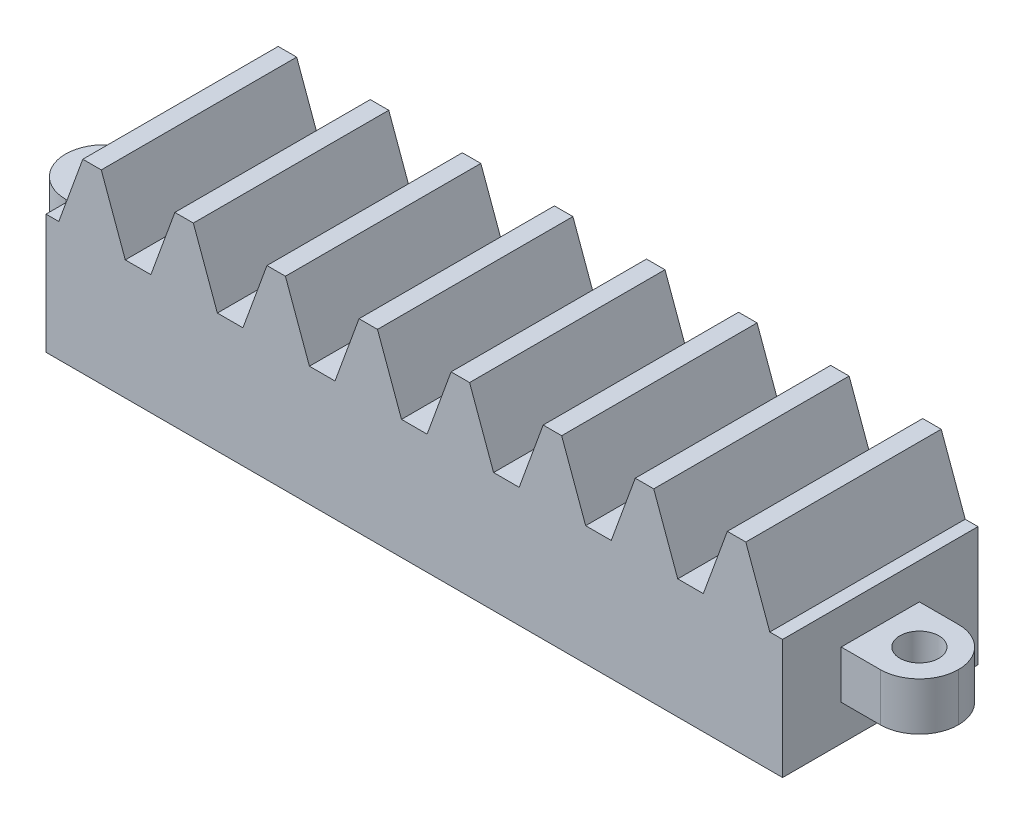
SolidWorks part; units mm, degrees
ref_plane "Plane1" through (0, 0, 0) normal (0, 0, 1) x (1, 0, 0)
ref_plane "Plane2" through (0, 0, 0) normal (0, 1, 0) x (1, 0, 0)
ref_plane "Plane3" through (0, 0, 0) normal (1, 0, 0) x (0, 0, -1)
sketch "Croquis3" plane through (0, 0, 0) normal (0, 0, 1) x (1, 0, 0)
  line B0 (32.3321, 6.125) -> (31.1037, 9.5)
  line B1 (33.6414, 6.125) -> (32.3321, 6.125)
  line B2 (34.8698, 9.5) -> (33.6414, 6.125)
  line B3 (35.8161, 9.5) -> (34.8698, 9.5)
  line B4 (37.0445, 6.125) -> (35.8161, 9.5)
  line B5 (37.6991, 6.125) -> (37.0445, 6.125)
  line B6 (0, 0) -> (37.6991, 0)
  line B7 (22.9073, 6.125) -> (21.6789, 9.5)
  line B8 (24.2166, 6.125) -> (22.9073, 6.125)
  line B9 (25.445, 9.5) -> (24.2166, 6.125)
  line B10 (26.3913, 9.5) -> (25.445, 9.5)
  line B11 (27.6197, 6.125) -> (26.3913, 9.5)
  line B12 (28.929, 6.125) -> (27.6197, 6.125)
  line B13 (30.1574, 9.5) -> (28.929, 6.125)
  line B14 (31.1037, 9.5) -> (30.1574, 9.5)
  line B15 (13.4825, 6.125) -> (12.2541, 9.5)
  line B16 (14.7918, 6.125) -> (13.4825, 6.125)
  line B17 (16.0202, 9.5) -> (14.7918, 6.125)
  line B18 (16.9665, 9.5) -> (16.0202, 9.5)
  line B19 (18.1949, 6.125) -> (16.9665, 9.5)
  line B20 (19.5042, 6.125) -> (18.1949, 6.125)
  line B21 (20.7326, 9.5) -> (19.5042, 6.125)
  line B22 (21.6789, 9.5) -> (20.7326, 9.5)
  line B23 (4.0577, 6.125) -> (2.8293, 9.5)
  line B24 (5.367, 6.125) -> (4.0577, 6.125)
  line B25 (6.5954, 9.5) -> (5.367, 6.125)
  line B26 (7.5417, 9.5) -> (6.5954, 9.5)
  line B27 (8.7701, 6.125) -> (7.5417, 9.5)
  line B28 (10.0794, 6.125) -> (8.7701, 6.125)
  line B29 (11.3078, 9.5) -> (10.0794, 6.125)
  line B30 (12.2541, 9.5) -> (11.3078, 9.5)
  line B31 (37.6991, 6.125) -> (37.6991, 0)
  line B32 (0, 6.125) -> (0, 0)
  line B33 (0.6547, 6.125) -> (0, 6.125)
  line B34 (1.8831, 9.5) -> (0.6547, 6.125)
  line B35 (2.8293, 9.5) -> (1.8831, 9.5)
sketch_block_instance "Bloque1-1"
sketch_block "Bloque1"
sketch "Croquis4" plane through (0, 0, 0) normal (0, 0, 1) x (1, 0, 0)
  line L0 (32.3321, 6.125) -> (31.1037, 9.5) construction
  line L1 (33.6414, 6.125) -> (32.3321, 6.125) construction
  line L2 (34.8698, 9.5) -> (33.6414, 6.125) construction
  line L3 (35.8161, 9.5) -> (34.8698, 9.5) construction
  line L4 (37.0445, 6.125) -> (35.8161, 9.5) construction
  line L5 (37.6991, 6.125) -> (37.0445, 6.125) construction
  line L6 (0, 0) -> (37.6991, 0) construction
  line L7 (22.9073, 6.125) -> (21.6789, 9.5) construction
  line L8 (24.2166, 6.125) -> (22.9073, 6.125) construction
  line L9 (25.445, 9.5) -> (24.2166, 6.125) construction
  line L10 (26.3913, 9.5) -> (25.445, 9.5) construction
  line L11 (27.6197, 6.125) -> (26.3913, 9.5) construction
  line L12 (28.929, 6.125) -> (27.6197, 6.125) construction
  line L13 (30.1574, 9.5) -> (28.929, 6.125) construction
  line L14 (31.1037, 9.5) -> (30.1574, 9.5) construction
  line L15 (13.4825, 6.125) -> (12.2541, 9.5) construction
  line L16 (14.7918, 6.125) -> (13.4825, 6.125) construction
  line L17 (16.0202, 9.5) -> (14.7918, 6.125) construction
  line L18 (16.9665, 9.5) -> (16.0202, 9.5) construction
  line L19 (18.1949, 6.125) -> (16.9665, 9.5) construction
  line L20 (19.5042, 6.125) -> (18.1949, 6.125) construction
  line L21 (20.7326, 9.5) -> (19.5042, 6.125) construction
  line L22 (21.6789, 9.5) -> (20.7326, 9.5) construction
  line L23 (4.0577, 6.125) -> (2.8293, 9.5) construction
  line L24 (5.367, 6.125) -> (4.0577, 6.125) construction
  line L25 (6.5954, 9.5) -> (5.367, 6.125) construction
  line L26 (7.5417, 9.5) -> (6.5954, 9.5) construction
  line L27 (8.7701, 6.125) -> (7.5417, 9.5) construction
  line L28 (10.0794, 6.125) -> (8.7701, 6.125) construction
  line L29 (11.3078, 9.5) -> (10.0794, 6.125) construction
  line L30 (12.2541, 9.5) -> (11.3078, 9.5) construction
  line L31 (37.6991, 6.125) -> (37.6991, 0) construction
  line L32 (0, 6.125) -> (0, 0) construction
  line L33 (0.6547, 6.125) -> (0, 6.125) construction
  line L34 (1.8831, 9.5) -> (0.6547, 6.125) construction
  line L35 (2.8293, 9.5) -> (1.8831, 9.5) construction
  line L36 (32.3321, 6.125) -> (31.1037, 9.5)
  line L37 (33.6414, 6.125) -> (32.3321, 6.125)
  line L38 (34.8698, 9.5) -> (33.6414, 6.125)
  line L39 (35.8161, 9.5) -> (34.8698, 9.5)
  line L40 (37.0445, 6.125) -> (35.8161, 9.5)
  line L41 (37.6991, 6.125) -> (37.0445, 6.125)
  line L42 (0, 0) -> (37.6991, 0)
  line L43 (22.9073, 6.125) -> (21.6789, 9.5)
  line L44 (24.2166, 6.125) -> (22.9073, 6.125)
  line L45 (25.445, 9.5) -> (24.2166, 6.125)
  line L46 (26.3913, 9.5) -> (25.445, 9.5)
  line L47 (27.6197, 6.125) -> (26.3913, 9.5)
  line L48 (28.929, 6.125) -> (27.6197, 6.125)
  line L49 (30.1574, 9.5) -> (28.929, 6.125)
  line L50 (31.1037, 9.5) -> (30.1574, 9.5)
  line L51 (13.4825, 6.125) -> (12.2541, 9.5)
  line L52 (14.7918, 6.125) -> (13.4825, 6.125)
  line L53 (16.0202, 9.5) -> (14.7918, 6.125)
  line L54 (16.9665, 9.5) -> (16.0202, 9.5)
  line L55 (18.1949, 6.125) -> (16.9665, 9.5)
  line L56 (19.5042, 6.125) -> (18.1949, 6.125)
  line L57 (20.7326, 9.5) -> (19.5042, 6.125)
  line L58 (21.6789, 9.5) -> (20.7326, 9.5)
  line L59 (4.0577, 6.125) -> (2.8293, 9.5)
  line L60 (5.367, 6.125) -> (4.0577, 6.125)
  line L61 (6.5954, 9.5) -> (5.367, 6.125)
  line L62 (7.5417, 9.5) -> (6.5954, 9.5)
  line L63 (8.7701, 6.125) -> (7.5417, 9.5)
  line L64 (10.0794, 6.125) -> (8.7701, 6.125)
  line L65 (11.3078, 9.5) -> (10.0794, 6.125)
  line L66 (12.2541, 9.5) -> (11.3078, 9.5)
  line L67 (37.6991, 6.125) -> (37.6991, 0)
  line L68 (0, 6.125) -> (0, 0)
  line L69 (0.6547, 6.125) -> (0, 6.125)
  line L70 (1.8831, 9.5) -> (0.6547, 6.125)
  line L71 (2.8293, 9.5) -> (1.8831, 9.5)
extrude "Extruir1" add sketch "Croquis4" along normal blind 10
sketch "Croquis5" plane through (37.6991, 0, 0) normal (1, 0, 0) x (0, 0, -1)
  line L0 (-10, 6.125) -> (0, 0) construction
  line L1 (-7, 4.2875) -> (-3, 4.2875)
  line L2 (-7, 4.2875) -> (-7, 1.8375)
  line L3 (-7, 1.8375) -> (-3, 1.8375)
  line L4 (-3, 4.2875) -> (-3, 1.8375)
  line L5 (-5, 3.0625) -> (0, 6.125) construction
  dimension "D1" = 4
  dimension "D2" = 2.45
extrude "Extruir2" add sketch "Croquis5" along normal blind 4
ref_plane "Plano1" through (18.8496, 0, 0) normal (1, 0, 0) x (0, 0, -1)
mirror "Simetría1" about plane through (18.8496, 0, 0) normal (1, 0, 0) of "Extruir2"
fillet "Redondeo1" radius 2 4 edges at (41.6991, 3.0625, 7) (41.6991, 3.0625, 3) (-4, 3.0625, 3) (-4, 3.0625, 7)
sketch "Croquis6" plane through (0, 4.2875, 0) normal (0, 1, 0) x (1, 0, 0)
  circle A0 centre (39.6991, -5) radius 1
  circle A1 centre (-2, -5) radius 1
  dimension "D1" = 2
extrude "Extruir3" cut sketch "Croquis6" against normal blind 4
